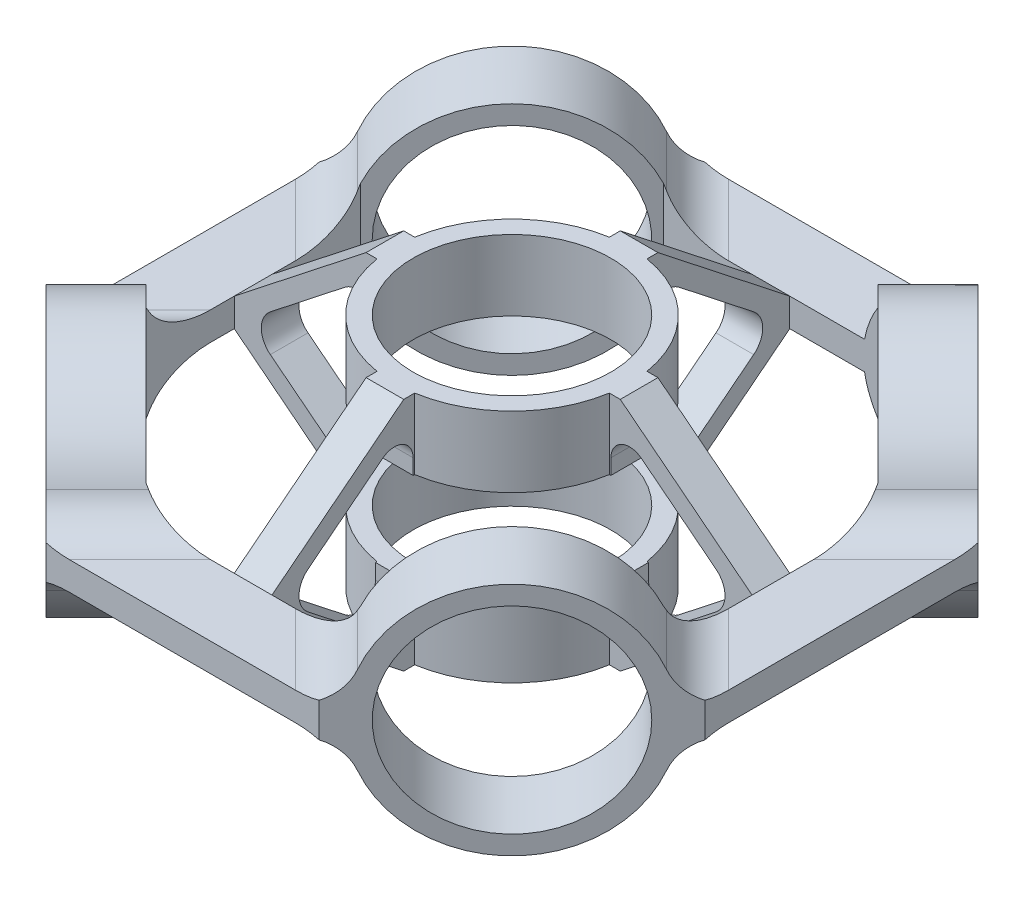
SolidWorks part; units mm, degrees
ref_plane "前视基准面" through (0, 0, 0) normal (0, 0, 1) x (1, 0, 0)
ref_plane "上视基准面" through (0, 0, 0) normal (0, 1, 0) x (1, 0, 0)
ref_plane "右视基准面" through (0, 0, 0) normal (1, 0, 0) x (0, 0, -1)
other "Configuration Table"
sketch "草图1" plane through (0, 0, 0) normal (0, 1, 0) x (1, 0, 0)
  line L0 (22.7817, 55) -> (-22.7817, 55)
  line L1 (70, -28.9949) -> (70, 28.9949)
  line L2 (70, 28.9949) -> (28.9949, 70)
  line L3 (28.9949, 70) -> (-28.9949, 70)
  line L4 (-28.9949, 70) -> (-70, 28.9949)
  line L5 (-70, 28.9949) -> (-70, -28.9949)
  line L6 (-70, -28.9949) -> (-28.9949, -70)
  line L7 (-28.9949, -70) -> (28.9949, -70)
  line L8 (28.9949, -70) -> (70, -28.9949)
  line L9 (-22.7817, 55) -> (-55, 22.7817)
  line L10 (-55, 22.7817) -> (-55, -22.7817)
  line L11 (-55, -22.7817) -> (-22.7817, -55)
  line L12 (-22.7817, -55) -> (22.7817, -55)
  line L13 (22.7817, -55) -> (55, -22.7817)
  line L14 (55, -22.7817) -> (55, 22.7817)
  line L15 (55, 22.7817) -> (22.7817, 55)
  circle A0 centre (0, 0) radius 70 construction
  circle A1 centre (0, 0) radius 25
  circle A2 centre (0, 0) radius 21
  dimension "D3" = 4
  dimension "D4" = 50
  dimension "D1" = 140
  dimension "D2" = 15
extrude "凸台-拉伸1" add sketch "草图1" against normal blind 15 from offset 25 contours A1 A2 region at (-24.2929, 0, 0)
extrude "凸台-拉伸2" add sketch "草图1<3>" along normal mid plane 6 separate body contours L7 L8 L1 L2 L3 L4 L5 L6 L15 L14 L13 L12 L11 L10 L9 L0 region at (48.0975, 0, 48.0975)
sketch "草图1<3>" plane through (0, 0, 0) normal (0, 1, 0) x (1, 0, 0) same geometry as "草图1"
extrude "凸台-拉伸7" add sketch "草图1<5>" along normal blind 15 from offset 25 separate body contours A1 A2 region at (-24.2929, 0, 0) offset against normal yes
sketch "草图1<5>" plane through (0, 0, 0) normal (0, 1, 0) x (1, 0, 0) same geometry as "草图1"
sketch "草图5" plane through (-49.4975, 0, -49.4975) normal (-0.7071, 0, -0.7071) x (-0.7071, 0, 0.7071)
  circle A0 centre (0, 0) radius 25
  circle A1 centre (0, 0) radius 21
  dimension "D1" = 50
  dimension "D2" = 4
extrude "凸台-拉伸9" add sketch "草图5" against normal blind 20
extrude "切除-拉伸4" cut sketch "草图5<2>" against normal blind 20 contours A1
sketch "草图5<2>" plane through (-49.4975, 0, -49.4975) normal (-0.7071, 0, -0.7071) x (-0.7071, 0, 0.7071) same geometry as "草图5"
mirror "镜向3" about plane through (0, 0, 0) normal (0, 0, 1) of "凸台-拉伸9", "切除-拉伸4"
mirror "镜向4" about plane through (0, 0, 0) normal (1, 0, 0) of "镜向3"
fillet "圆角4" radius 10 14 edges at (-25.9238, 3, -61.0237) (-25.9238, -3, -61.0237) (-61.0237, -3, -25.9238) (-61.0237, 3, -25.9238) (61.0237, -3, -25.9238) (61.0237, 3, -25.9238) (61.0237, -3, 25.9238) (61.0237, 3, 25.9238) (25.9238, 3, 61.0237) (25.9238, -3, 61.0237) (-25.9238, -3, 61.0237) (-25.9238, 3, 61.0237) (-61.0237, -3, 25.9238) (-61.0237, 3, 25.9238)
extrude "切除-拉伸5" cut sketch "草图1<6>" against normal mid plane 50 contours L14 L15 L0 L9 L10 L11 L12 L13 A1 region at (37.7909, 0, -37.7909)
sketch "草图1<6>" plane through (0, 0, 0) normal (0, 1, 0) x (1, 0, 0) same geometry as "草图1"
sketch "草图7" plane through (0, 0, 0) normal (0, 0, 1) x (1, 0, 0)
  line L0 (22.5, 25) -> (27, 25)
  line L1 (25, 25) -> (-25, 25) construction
  line L2 (21, 25) -> (-21, 25) construction
  line L3 (27, 25) -> (55, 3)
  line L4 (55, 3) -> (55, -3)
  line L5 (0, 43.5598) -> (0, 0) construction
  line L6 (0, 0) -> (73.7541, 0) construction
  line L7 (22.5, 25) -> (22.5, 10)
  line L8 (-21, 10) -> (21, 10) construction
  line L9 (-25, 10) -> (25, 10) construction
  line L10 (22.5, 10) -> (25, 10)
  line L11 (25, 10) -> (25, 13.2546)
  line L12 (31.4713, 16.3998) -> (47.34, 3.9316)
  line L13 (25, 10) -> (25, 25) construction
  line L14 (31.4713, -16.3998) -> (47.34, -3.9316)
  line L15 (25, -10) -> (25, -13.2546)
  line L16 (22.5, -10) -> (25, -10)
  line L17 (22.5, -25) -> (22.5, -10)
  line L18 (27, -25) -> (55, -3)
  line L19 (22.5, -25) -> (27, -25)
  arc A0 (25, 13.2546) -> (31.4713, 16.3998) centre (29, 13.2546) cw
  arc A1 (25, -13.2546) -> (31.4713, -16.3998) centre (29, -13.2546) ccw
  arc A2 (47.34, 3.9316) -> (47.34, -3.9316) centre (44.2509, 0) cw
  point P43 (52.3438, 0)
  dimension "D3" = 4
  dimension "D5" = 5
  dimension "D1" = 54
  dimension "D2" = 45
  dimension "D4" = 4
extrude "凸台-拉伸10" add sketch "草图7" along normal mid plane 8
pattern_circular "阵列(圆周)1" count 4 over 360 about axis through (0, 25, 0) along (0, 1, 0) of "凸台-拉伸10"
